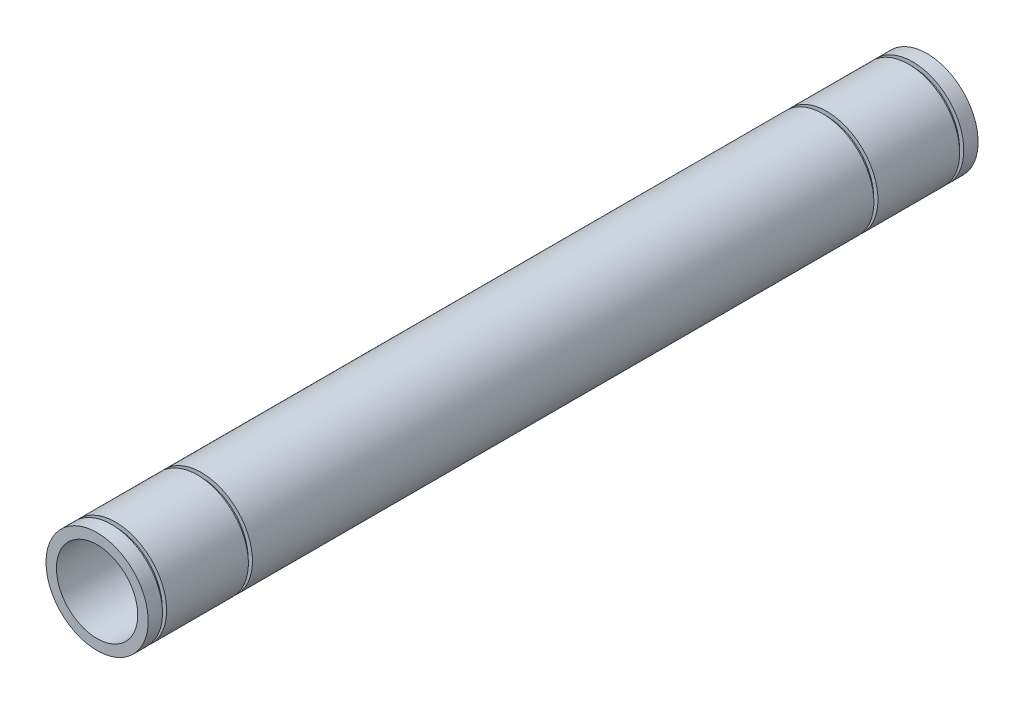
SolidWorks part; units mm, degrees
material "6061-T6 (SS)"
ref_plane "Front Plane" through (0, 0, 0) normal (0, 0, 1) x (1, 0, 0)
ref_plane "Top Plane" through (0, 0, 0) normal (0, 1, 0) x (1, 0, 0)
ref_plane "Right Plane" through (0, 0, 0) normal (1, 0, 0) x (0, 0, -1)
sketch "Sketch1" plane through (0, 0, 0) normal (0, 0, 1) x (1, 0, 0)
  circle A0 centre (0, 0) radius 25
  circle A1 centre (0, 0) radius 19.9
  dimension "D1" = 50
  dimension "D2" = 39.8
extrude "Body" add sketch "Sketch1" along normal blind 406
sketch "Sketch2" plane through (0, 0, 0) normal (1, 0, 0) x (0, 0, -1)
  line L0 (-348, 25) -> (-348, -25) construction
  line L1 (0, 25) -> (-406, 25) construction
  line L2 (-406, -25) -> (0, -25) construction
  line L3 (-406, 25) -> (-406, -25) construction
  line L4 (0, 0) -> (-406, 0) construction
  line L5 (-406, 22.9) -> (0, 22.9) construction
  line L6 (0, -25) -> (0, 25) construction
  line L7 (-203, 25) -> (-203, -25) construction
  line L8 (-399, 25) -> (-397, 25)
  line L9 (-399, 25) -> (-399, 22.9)
  line L10 (-399, 22.9) -> (-397, 22.9)
  line L11 (-397, 25) -> (-397, 22.9)
  line L12 (-357, 25) -> (-355, 25)
  line L13 (-357, 25) -> (-357, 22.9)
  line L14 (-357, 22.9) -> (-355, 22.9)
  line L15 (-355, 25) -> (-355, 22.9)
  line L16 (-49, 22.9) -> (-51, 22.9)
  line L17 (-49, 25) -> (-49, 22.9)
  line L18 (-49, 25) -> (-51, 25)
  line L19 (-51, 25) -> (-51, 22.9)
  line L20 (-7, 22.9) -> (-9, 22.9)
  line L21 (-9, 25) -> (-9, 22.9)
  line L22 (-7, 25) -> (-9, 25)
  line L23 (-7, 25) -> (-7, 22.9)
  dimension "D1" = 58
  dimension "D2" = 22.9
  dimension "D3" = 2
  dimension "D4" = 2
  dimension "D5" = 9
  dimension "D6" = 49
revolve "Ret Ring Grooves" cut sketch "Sketch2" angle 360 about L4
equation "\"shaft_diameter\"= 50.0mm"
equation "\"ret_ring_inner_diameter\"= 45.8mm"
equation "\"ret_ring_thickness\"= 2.0mm"
equation "\"ret_ring_1_pos\"= 9.0mm"
equation "\"ret_ring_2_pos\"= 49.0mm"
equation "\"ref_length\"= 53.0mm"
equation "\"length\"= 406.0mm"
equation "\"D1@Sketch1\"=\"shaft_diameter\""
equation "\"D2@Sketch1\"=\"ret_ring_inner_diameter\"-6"
equation "\"D1@Body\" = \"length\""
equation "\"D2@Sketch2\"=\"ret_ring_inner_diameter\"/2"
equation "\"D3@Sketch2\"=\"ret_ring_thickness\""
equation "\"D4@Sketch2\"=\"ret_ring_thickness\""
equation "\"D5@Sketch2\"=\"ret_ring_1_pos\""
equation "\"D6@Sketch2\"=\"ret_ring_2_pos\""
